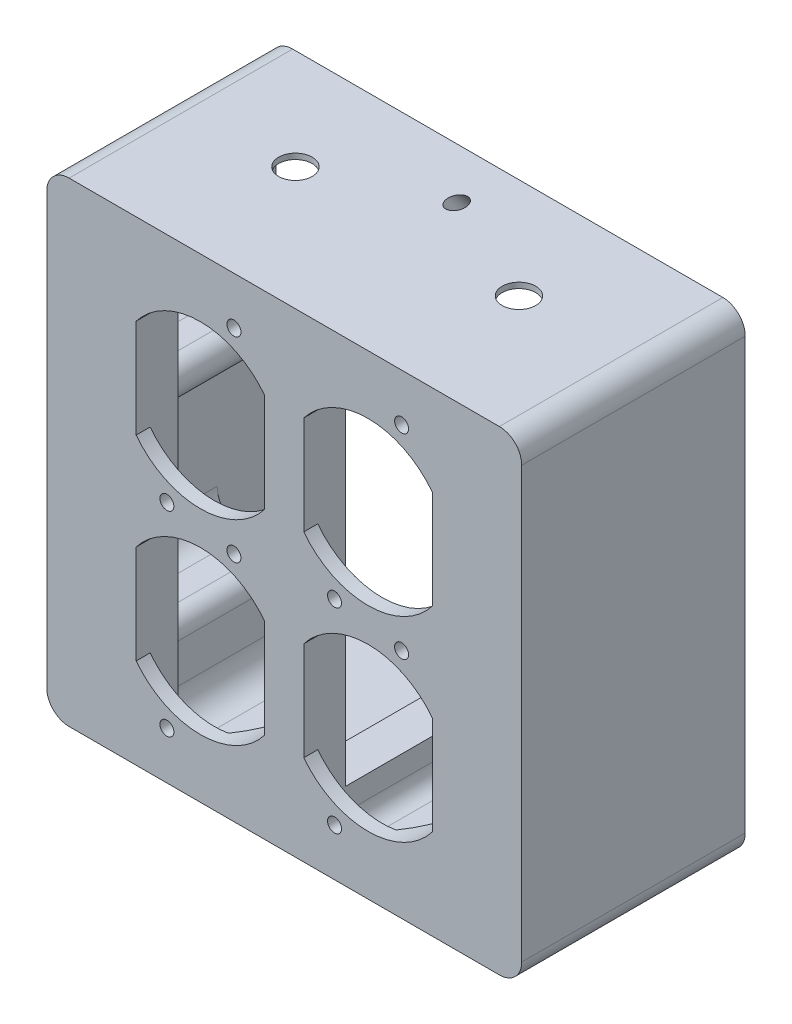
SolidWorks part; units mm, degrees
ref_plane "Front Plane" through (0, 0, 0) normal (0, 0, 1) x (1, 0, 0)
ref_plane "Top Plane" through (0, 0, 0) normal (0, 1, 0) x (1, 0, 0)
ref_plane "Right Plane" through (0, 0, 0) normal (1, 0, 0) x (0, 0, -1)
sketch "Sketch1" plane through (0, 0, 0) normal (0, 0, 1) x (1, 0, 0)
  line L1 (-42.5, -42.5) -> (42.5, -42.5)
  line L2 (-42.5, -42.5) -> (-42.5, 42.5)
  line L3 (-42.5, 42.5) -> (42.5, 42.5)
  line L4 (42.5, -42.5) -> (42.5, 42.5)
  line L5 (-42.5, -42.5) -> (42.5, 42.5) construction
  line L6 (-42.5, 42.5) -> (42.5, -42.5) construction
  point P0 (0, 0)
  dimension "D1" = 85
  dimension "D2" = 85
extrude "Boss-Extrude1" add sketch "Sketch1" along normal blind 40
sketch "Sketch8" plane through (0, 0, 0) normal (0, 0, -1) x (-1, 0, 0)
  line L14 (41.5, -41.5) -> (41.5, 41.5)
  line L15 (-41.5, -41.5) -> (41.5, -41.5)
  line L16 (-41.5, 41.5) -> (-41.5, -41.5)
  line L17 (41.5, 41.5) -> (-41.5, 41.5)
  line L18 (41.5, -38.5) -> (41.5, 38.5)
  line L19 (-38.5, -41.5) -> (38.5, -41.5)
  line L20 (-41.5, 38.5) -> (-41.5, -38.5)
  line L21 (38.5, 41.5) -> (-38.5, 41.5)
  arc A0 (-38.5, -41.5) -> (-41.5, -38.5) centre (-38.5, -38.5) cw
  arc A1 (41.5, -38.5) -> (38.5, -41.5) centre (38.5, -38.5) cw
  arc A2 (41.5, 38.5) -> (38.5, 41.5) centre (38.5, 38.5) ccw
  arc A3 (-41.5, 38.5) -> (-38.5, 41.5) centre (-38.5, 38.5) cw
  dimension "D2" = 3
  dimension "D1" = 1
extrude "Cut-Extrude4" cut sketch "Sketch8" against normal offset from surface (37.5 mm away) 2.5 up to face at (0, 0, 40)
fillet "Fillet4" radius 4 4 edges at (42.5, 42.5, 20) (42.5, -42.5, 20) (-42.5, 42.5, 20) (-42.5, -42.5, 20)
sketch "Sketch2" plane through (0, 0, 40) normal (0, 0, 1) x (1, 0, 0)
  line L2 (-26.5, 8.6682) -> (-26.5, 26.3318)
  line L4 (-3.5, 8.6682) -> (-3.5, 26.3318)
  line L5 (-26.5, 8.6682) -> (-3.5, 26.3318) construction
  line L6 (-26.5, 26.3318) -> (-3.5, 8.6682) construction
  arc A0 (-26.5, 26.3318) -> (-3.5, 26.3318) centre (-15, 17.5) cw
  arc A1 (-26.5, 8.6682) -> (-3.5, 8.6682) centre (-15, 17.5) ccw
  point P0 (-15, 17.5)
  point P7 (-15, 3)
  point P9 (-15, 32)
  dimension "D1" = 23
  dimension "D2" = 17.5
  dimension "D3" = 15
  dimension "D4" = 29
extrude "Cut-Extrude1" cut sketch "Sketch2" against normal through all
sketch "Sketch3" plane through (0, 0, 40) normal (0, 0, 1) x (1, 0, 0)
  line L0 (-15, 32) -> (-15, 3) construction
  circle A0 centre (-9, 34) radius 1.25
  circle A1 centre (-21, 1) radius 1.25
  arc A2 (-3.5, 26.3318) -> (-26.5, 26.3318) centre (-15, 17.5) ccw construction
  arc A3 (-26.5, 8.6682) -> (-3.5, 8.6682) centre (-15, 17.5) ccw construction
  point P12 (-15, 17.5)
  dimension "D3" = 2.5
  dimension "D1" = 6
  dimension "D2" = 6
  dimension "D4" = 16.5
  dimension "D5" = 16.5
extrude "Cut-Extrude6" cut sketch "Sketch3" against normal through all
pattern_linear "LPattern1" count 2 spacing 35 along (0, -1, 0) count 2 spacing 30 along (1, 0, 0) of "Cut-Extrude1", "Cut-Extrude6"
sketch "Sketch19" plane through (0, 0, 37.5) normal (0, 0, -1) x (-1, 0, 0)
  line L0 (38.5, -41.5) -> (-38.5, -41.5) construction
  line L1 (-38.5, 41.5) -> (-26.5, 41.5)
  line L2 (-41.5, 38.5) -> (-41.5, -38.5)
  line L3 (-38.5, -41.5) -> (-26.5, -41.5)
  line L4 (-26.5, 41.5) -> (-26.5, -41.5)
  line L5 (-38.5, 41.5) -> (38.5, 41.5) construction
  line L6 (-3.5, 41.5) -> (3.5, 41.5)
  line L7 (-3.5, 41.5) -> (-3.5, -41.5)
  line L8 (-3.5, -41.5) -> (3.5, -41.5)
  line L9 (3.5, 41.5) -> (3.5, -41.5)
  line L10 (-26.5, 26.3318) -> (-26.5, 8.6682) construction
  line L11 (38.5, 41.5) -> (26.5, 41.5)
  line L12 (41.5, 38.5) -> (41.5, -38.5)
  line L13 (38.5, -41.5) -> (26.5, -41.5)
  line L14 (26.5, 41.5) -> (26.5, -41.5)
  line L15 (-3.5, 8.6682) -> (-3.5, 26.3318) construction
  line L16 (3.5, 26.3318) -> (3.5, 8.6682) construction
  line L17 (26.5, 8.6682) -> (26.5, 26.3318) construction
  line L18 (-38.5, 41.5) -> (38.5, 41.5) construction
  line L19 (-41.5, -38.5) -> (-41.5, 38.5) construction
  line L20 (41.5, 38.5) -> (41.5, -38.5) construction
  arc A0 (-41.5, -38.5) -> (-38.5, -41.5) centre (-38.5, -38.5) ccw
  arc A1 (-38.5, 41.5) -> (-41.5, 38.5) centre (-38.5, 38.5) ccw
  arc A2 (41.5, -38.5) -> (38.5, -41.5) centre (38.5, -38.5) cw
  arc A3 (38.5, 41.5) -> (41.5, 38.5) centre (38.5, 38.5) cw
  point P34 (-41.5, 41.5)
  point P41 (41.5, 41.5)
  dimension "D1" = 3
  dimension "D2" = 3
extrude "Boss-Extrude7" add sketch "Sketch19" along normal blind 5
chamfer "Chamfer1" distance 9 angle 45 4 edges at (-3.5, -33.9159, 37.5) (26.5, -33.9159, 37.5) (-26.5, 33.9159, 37.5) (3.5, 33.9159, 37.5)
sketch "Sketch23" plane through (0, 0, 32.5) normal (0, 0, -1) x (-1, 0, 0)
  line L0 (-41.5, 38.5) -> (-41.5, -38.5) construction
  line L1 (-38.5, -41.5) -> (-29, -41.5)
  line L2 (-41.5, -38.5) -> (-41.5, -26.5)
  line L3 (-41.5, -26.5) -> (-32, -26.5)
  line L4 (-29, -41.5) -> (-29, -29.5)
  line L5 (-41.5, 12.5) -> (-32, 12.5)
  line L6 (-41.5, 12.5) -> (-41.5, 6.5)
  line L7 (-41.5, 6.5) -> (-32, 6.5)
  line L8 (-41.5, 38.5) -> (-41.5, -38.5) construction
  line L9 (-38.5, -41.5) -> (-22.5, -41.5) construction
  arc A0 (-32, 12.5) -> (-32, 6.5) centre (-32, 9.5) cw
  arc A1 (-32, -26.5) -> (-29, -29.5) centre (-32, -29.5) cw
  arc A2 (-38.5, -41.5) -> (-41.5, -38.5) centre (-38.5, -38.5) cw
  point P21 (-41.5, -41.5)
  dimension "D1" = 3
  dimension "D5" = 3
  dimension "D2" = 32
  dimension "D3" = 6
  dimension "D4" = 12
  dimension "39" = 39
extrude "Boss-Extrude8" add sketch "Sketch23" along normal blind 22
sketch "Sketch25" plane through (0, 0, 10.5) normal (0, 0, -1) x (-1, 0, 0)
  circle A0 centre (-32, -29.5) radius 1.25
  circle A1 centre (-32, 9.5) radius 1.25
  dimension "D1" = 2.5
extrude "Cut-Extrude10" cut sketch "Sketch25" against normal blind 5
mirror "Mirror5" about plane through (0, 0, 0) normal (1, 0, 0) of "Cut-Extrude10", "Boss-Extrude8"
sketch "Sketch14" plane through (0, 0, 40) normal (0, 0, 1) x (1, 0, 0)
  line L0 (-42.5, 38.5) -> (-42.5, -38.5) construction
  line L1 (-38, 33.5) -> (-42.5, 33.5)
  line L2 (-42.5, 38.5) -> (-42.5, -38.5) construction
  line L3 (-42.5, 33.5) -> (-42.5, 38)
  line L4 (-38, 42.5) -> (-33.5, 42.5)
  line L5 (-33.5, 42.5) -> (-33.5, 38)
  arc A0 (-38, 42.5) -> (-42.5, 38) centre (-38, 38) ccw
  arc A2 (-38, 33.5) -> (-33.5, 38) centre (-38, 38) ccw
  dimension "D1" = 38
  dimension "D2" = 38
extrude "Boss-Extrude6" add sketch "Sketch14" against normal up to surface (40 mm away) up to face at (0, 0, 0)
sketch "Sketch15" plane through (0, 0, 0) normal (0, 0, -1) x (-1, 0, 0)
  circle A0 centre (38, 38) radius 1.25
  arc A1 (33.5, 38) -> (38, 33.5) centre (38, 38) ccw construction
  dimension "D1" = 2.5
extrude "Cut-Extrude7" cut sketch "Sketch15" against normal blind 10
sketch "Sketch28" plane through (0, 0, 0) normal (0, 0, -1) x (-1, 0, 0)
  line L0 (33.5, 41.5) -> (38.5, 41.5)
  line L1 (33.5, 41.5) -> (-38.5, 41.5) construction
  line L2 (33.5, 38) -> (33.5, 41.5) construction
  line L3 (41.5, 38.5) -> (41.5, 33.5)
  arc A0 (38.5, 41.5) -> (41.5, 38.5) centre (38.5, 38.5) cw
  dimension "D1" = 3
extrude "Cut-Extrude-Thin1" cut sketch "Sketch28" against normal blind 2 thin thin type one direction wall 1
mirror "Mirror3" about plane through (0, 0, 0) normal (1, 0, 0) of "Cut-Extrude-Thin1", "Boss-Extrude6", "Cut-Extrude7"
mirror "Mirror4" about plane through (0, 0, 0) normal (0, 1, 0) of "Mirror3"
sketch "Sketch16" plane through (0, 42.5, 0) normal (0, 1, 0) x (1, 0, 0)
  line L0 (20, -18) -> (-20, -18) construction
  line L2 (0, -18) -> (0, 0) construction
  line L3 (38.5, 0) -> (-38.5, 0) construction
  circle A0 centre (20, -18) radius 3
  circle A1 centre (-20, -18) radius 3
  dimension "D1" = 6
  dimension "D2" = 40
  dimension "D3" = 18
extrude "Cut-Extrude8" cut sketch "Sketch16" against normal up to next
sketch "Sketch26" plane through (0, 0, 0) normal (1, 0, 0) x (0, 0, -1)
  line L1 (-40, -42.5) -> (0, -42.5)
  line L2 (-40, -42.5) -> (-40, -34.5)
  line L3 (-40, -34.5) -> (-9.534, -34.5)
  line L4 (0, -42.5) -> (-9.534, -34.5)
  point P5 (-4.767, -38.5)
  dimension "D1" = 8
  dimension "D2" = 40
  dimension "D3" = 40
extrude "Boss-Extrude9" add sketch "Sketch26" along normal mid plane 7
sketch "Sketch27" plane through (0, -24.94, 20.9272) normal (0, 0.766, -0.6428) x (1, 0, 0)
  line L0 (3.5, 14.8727) -> (-3.5, 25.7627) construction
  circle A0 centre (0, 20.3177) radius 1.5
  dimension "D1" = 3
extrude "Cut-Extrude11" cut sketch "Sketch27" against normal through all
mirror "Mirror6" about plane through (0, 0, 0) normal (0, 1, 0) of "Cut-Extrude11", "Boss-Extrude9"
fillet "Fillet6" radius 5 8 edges at (41.5, 12.5, 21.5) (41.5, 6.5, 21.5) (29, -41.5, 21.5) (41.5, -26.5, 21.5) (-41.5, 12.5, 21.5) (-41.5, 6.5, 21.5) (-29, -41.5, 21.5) (-41.5, -26.5, 21.5)
fillet "Fillet7" radius 3 4 edges at (3.5, -41.5, 19.3459) (-3.5, -41.5, 16.8459) (3.5, 41.5, 16.8459) (-3.5, 41.5, 19.3459)
